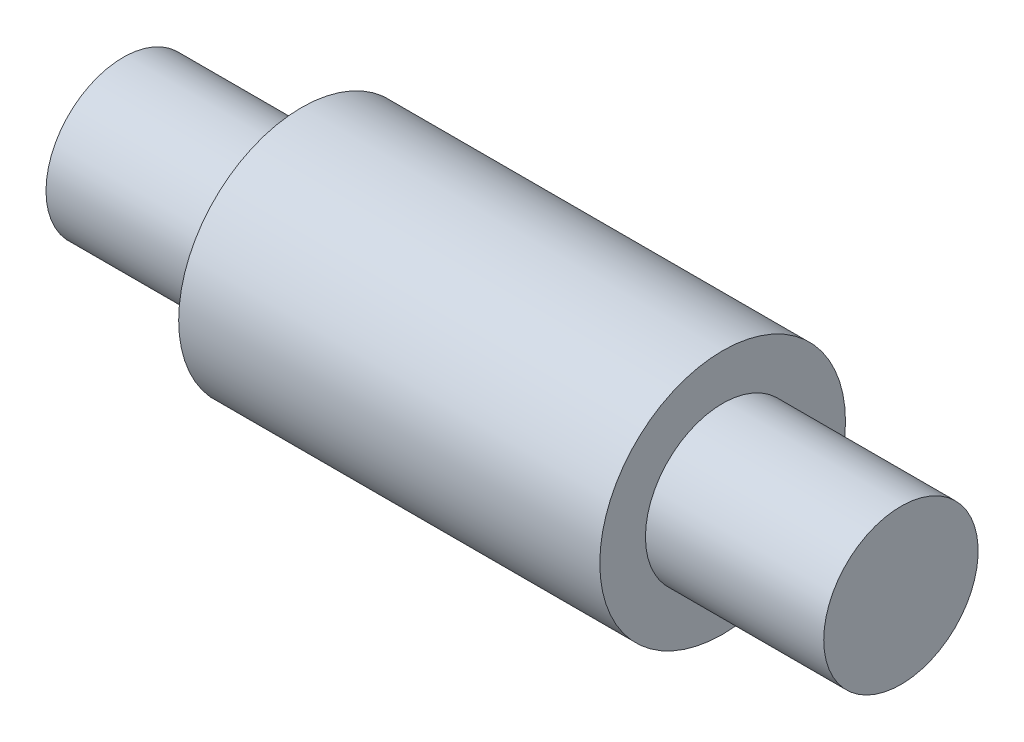
SolidWorks part; units mm, degrees
ref_plane "Front Plane" through (0, 0, 0) normal (0, 0, 1) x (1, 0, 0)
ref_plane "Top Plane" through (0, 0, 0) normal (0, 1, 0) x (1, 0, 0)
ref_plane "Right Plane" through (0, 0, 0) normal (1, 0, 0) x (0, 0, -1)
sketch "CV_Western_4M Sketch" plane through (0, 0, 0) normal (0, 0, 1) x (1, 0, 0)
  line L0 (-1000, 0) -> (1000, 0) construction
  line L1 (12.7, 0) -> (12.7, 5.5)
  line L2 (12.7, 5.5) -> (0, 5.5)
  line L3 (0, 5.5) -> (0, 8.75)
  line L4 (0, 8.75) -> (-30, 8.75)
  line L5 (-30, 8.75) -> (-30, 5.5)
  line L6 (-30, 5.5) -> (-42.7, 5.5)
  line L7 (-42.7, 5.5) -> (-42.7, 0)
  line L8 (-42.7, 0) -> (12.7, 0)
revolve "CV_Western_4M" add sketch "CV_Western_4M Sketch" angle 360 about L0
ref_axis "Engine Axis" through (15.47, 0, 0) along (-1, 0, 0)
